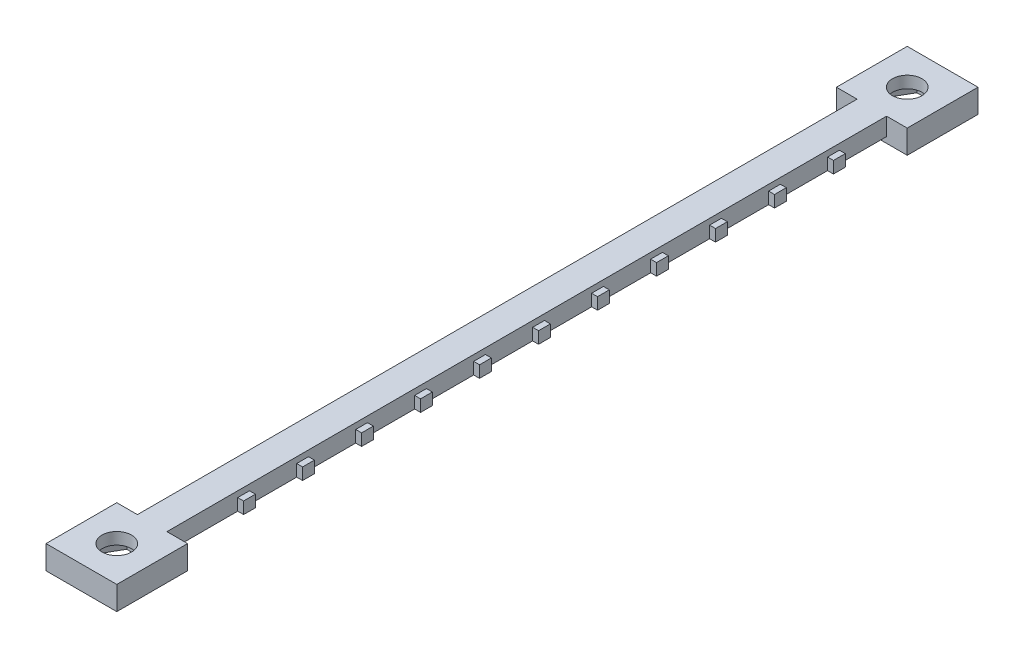
SolidWorks part; units mm, degrees
ref_plane "Front Plane" through (0, 0, 0) normal (0, 0, 1) x (1, 0, 0)
ref_plane "Top Plane" through (0, 0, 0) normal (0, 1, 0) x (1, 0, 0)
ref_plane "Right Plane" through (0, 0, 0) normal (1, 0, 0) x (0, 0, -1)
sketch "Sketch1" plane through (0, 0, 0) normal (0, 1, 0) x (1, 0, 0)
  line L0 (7.2267, 6.096) -> (7.2267, 18.096)
  line L1 (12.2267, 6.096) -> (12.2267, 18.096)
  line L2 (7.2267, 128.096) -> (3.7267, 128.096)
  line L3 (12.2267, 128.096) -> (15.7267, 128.096)
  line L4 (3.7267, 128.096) -> (3.7267, 140.096)
  line L5 (15.7267, 128.096) -> (15.7267, 140.096)
  line L6 (3.7267, 140.096) -> (15.7267, 140.096)
  line L7 (7.2267, 6.096) -> (3.7267, 6.096)
  line L8 (12.2267, 6.096) -> (15.7267, 6.096)
  line L9 (3.7267, 6.096) -> (3.7267, -5.904)
  line L10 (15.7267, 6.096) -> (15.7267, -5.904)
  line L11 (3.7267, -5.904) -> (15.7267, -5.904)
  line L12 (7.2267, 120.096) -> (7.2267, 128.096)
  line L13 (7.2267, 6.096) -> (7.2267, 128.096) construction
  line L14 (-994.5233, 128.096) -> (49005.4767, 128.096) construction
  line L15 (6.2267, 120.096) -> (7.2267, 120.096)
  line L18 (6.2267, 118.096) -> (7.2267, 118.096)
  line L19 (6.2267, 110.096) -> (7.2267, 110.096)
  line L20 (6.2267, 108.096) -> (7.2267, 108.096)
  line L21 (6.2267, 100.096) -> (7.2267, 100.096)
  line L22 (6.2267, 98.096) -> (7.2267, 98.096)
  line L23 (6.2267, 90.096) -> (7.2267, 90.096)
  line L24 (6.2267, 88.096) -> (7.2267, 88.096)
  line L25 (6.2267, 80.096) -> (7.2267, 80.096)
  line L26 (6.2267, 78.096) -> (7.2267, 78.096)
  line L27 (6.2267, 70.096) -> (7.2267, 70.096)
  line L28 (6.2267, 68.096) -> (7.2267, 68.096)
  line L29 (6.2267, 60.096) -> (7.2267, 60.096)
  line L30 (6.2267, 58.096) -> (7.2267, 58.096)
  line L31 (6.2267, 50.096) -> (7.2267, 50.096)
  line L32 (6.2267, 48.096) -> (7.2267, 48.096)
  line L33 (6.2267, 40.096) -> (7.2267, 40.096)
  line L34 (6.2267, 38.096) -> (7.2267, 38.096)
  line L35 (6.2267, 30.096) -> (7.2267, 30.096)
  line L36 (6.2267, 28.096) -> (7.2267, 28.096)
  line L37 (6.2267, 20.096) -> (7.2267, 20.096)
  line L38 (6.2267, 18.096) -> (7.2267, 18.096)
  line L39 (-994.5233, 118.096) -> (49005.4767, 118.096) construction
  line L40 (-994.5233, 120.096) -> (49005.4767, 120.096) construction
  line L41 (12.2267, 120.096) -> (12.2267, 128.096)
  line L42 (12.2267, 6.096) -> (12.2267, 128.096) construction
  line L43 (6.2267, 118.096) -> (6.2267, 120.096)
  line L44 (12.2267, 118.096) -> (13.2267, 118.096)
  line L45 (12.2267, 120.096) -> (13.2267, 120.096)
  line L46 (7.2267, 110.096) -> (7.2267, 118.096)
  line L47 (12.2267, 110.096) -> (12.2267, 118.096)
  line L48 (13.2267, 118.096) -> (13.2267, 120.096)
  line L49 (-994.5233, 110.096) -> (49005.4767, 110.096) construction
  line L50 (-994.5233, 108.096) -> (49005.4767, 108.096) construction
  line L51 (13.2267, 108.096) -> (13.2267, 110.096)
  line L52 (-994.5233, 100.096) -> (49005.4767, 100.096) construction
  line L53 (12.2267, 110.096) -> (13.2267, 110.096)
  line L54 (12.2267, 108.096) -> (13.2267, 108.096)
  line L55 (12.2267, 100.096) -> (13.2267, 100.096)
  line L56 (12.2267, 98.096) -> (13.2267, 98.096)
  line L57 (-994.5233, 98.096) -> (49005.4767, 98.096) construction
  line L58 (12.2267, 90.096) -> (13.2267, 90.096)
  line L59 (-994.5233, 90.096) -> (49005.4767, 90.096) construction
  line L60 (12.2267, 88.096) -> (13.2267, 88.096)
  line L61 (-994.5233, 88.096) -> (49005.4767, 88.096) construction
  line L62 (12.2267, 80.096) -> (13.2267, 80.096)
  line L63 (-994.5233, 80.096) -> (49005.4767, 80.096) construction
  line L64 (12.2267, 78.096) -> (13.2267, 78.096)
  line L65 (-994.5233, 78.096) -> (49005.4767, 78.096) construction
  line L66 (12.2267, 70.096) -> (13.2267, 70.096)
  line L67 (-994.5233, 70.096) -> (49005.4767, 70.096) construction
  line L68 (12.2267, 68.096) -> (13.2267, 68.096)
  line L69 (-994.5233, 68.096) -> (49005.4767, 68.096) construction
  line L70 (12.2267, 60.096) -> (13.2267, 60.096)
  line L71 (-994.5233, 60.096) -> (49005.4767, 60.096) construction
  line L72 (12.2267, 58.096) -> (13.2267, 58.096)
  line L73 (-994.5233, 58.096) -> (49005.4767, 58.096) construction
  line L74 (12.2267, 50.096) -> (13.2267, 50.096)
  line L75 (-994.5233, 50.096) -> (49005.4767, 50.096) construction
  line L76 (12.2267, 48.096) -> (13.2267, 48.096)
  line L77 (-994.5233, 48.096) -> (49005.4767, 48.096) construction
  line L78 (12.2267, 40.096) -> (13.2267, 40.096)
  line L79 (-994.5233, 40.096) -> (49005.4767, 40.096) construction
  line L80 (12.2267, 38.096) -> (13.2267, 38.096)
  line L81 (-994.5233, 38.096) -> (49005.4767, 38.096) construction
  line L82 (12.2267, 30.096) -> (13.2267, 30.096)
  line L83 (-994.5233, 30.096) -> (49005.4767, 30.096) construction
  line L84 (12.2267, 28.096) -> (13.2267, 28.096)
  line L85 (-994.5233, 28.096) -> (49005.4767, 28.096) construction
  line L86 (12.2267, 20.096) -> (13.2267, 20.096)
  line L87 (-994.5233, 20.096) -> (49005.4767, 20.096) construction
  line L88 (12.2267, 18.096) -> (13.2267, 18.096)
  line L89 (-994.5233, 18.096) -> (49005.4767, 18.096) construction
  line L90 (13.2267, 18.096) -> (13.2267, 20.096)
  line L91 (6.2267, 108.096) -> (6.2267, 110.096)
  line L92 (12.2267, 100.096) -> (12.2267, 108.096)
  line L93 (7.2267, 100.096) -> (7.2267, 108.096)
  line L94 (7.2267, 90.096) -> (7.2267, 98.096)
  line L95 (12.2267, 90.096) -> (12.2267, 98.096)
  line L96 (13.2267, 98.096) -> (13.2267, 100.096)
  line L97 (6.2267, 98.096) -> (6.2267, 100.096)
  line L98 (12.2267, 80.096) -> (12.2267, 88.096)
  line L99 (7.2267, 80.096) -> (7.2267, 88.096)
  line L100 (7.2267, 70.096) -> (7.2267, 78.096)
  line L101 (12.2267, 70.096) -> (12.2267, 78.096)
  line L102 (12.2267, 60.096) -> (12.2267, 68.096)
  line L103 (7.2267, 60.096) -> (7.2267, 68.096)
  line L104 (13.2267, 88.096) -> (13.2267, 90.096)
  line L105 (13.2267, 78.096) -> (13.2267, 80.096)
  line L106 (13.2267, 68.096) -> (13.2267, 70.096)
  line L107 (13.2267, 58.096) -> (13.2267, 60.096)
  line L108 (6.2267, 58.096) -> (6.2267, 60.096)
  line L109 (6.2267, 68.096) -> (6.2267, 70.096)
  line L110 (6.2267, 78.096) -> (6.2267, 80.096)
  line L111 (6.2267, 88.096) -> (6.2267, 90.096)
  line L112 (12.2267, 50.096) -> (12.2267, 58.096)
  line L113 (7.2267, 50.096) -> (7.2267, 58.096)
  line L114 (7.2267, 40.096) -> (7.2267, 48.096)
  line L115 (12.2267, 40.096) -> (12.2267, 48.096)
  line L116 (7.2267, 30.096) -> (7.2267, 38.096)
  line L117 (12.2267, 30.096) -> (12.2267, 38.096)
  line L118 (7.2267, 20.096) -> (7.2267, 28.096)
  line L119 (12.2267, 20.096) -> (12.2267, 28.096)
  line L120 (6.2267, 18.096) -> (6.2267, 20.096)
  line L121 (6.2267, 28.096) -> (6.2267, 30.096)
  line L122 (6.2267, 38.096) -> (6.2267, 40.096)
  line L123 (6.2267, 48.096) -> (6.2267, 50.096)
  line L124 (13.2267, 48.096) -> (13.2267, 50.096)
  line L125 (13.2267, 28.096) -> (13.2267, 30.096)
  line L126 (13.2267, 38.096) -> (13.2267, 40.096)
  point P20 (5.4767, 128.096)
  dimension "D1" = 5
  dimension "D4" = 8
  dimension "D5" = 2
  dimension "D6" = 10
  dimension "D7" = 20
  dimension "D8" = 40
  dimension "D9" = 40
extrude "Boss-Extrude1" add sketch "Sketch1" along normal blind 2
sketch "Sketch2" plane through (0, 2, 0) normal (0, 1, 0) x (1, 0, 0)
  line L0 (3.7267, 140.096) -> (15.7267, 140.096)
  line L1 (15.7267, 140.096) -> (15.7267, 128.096)
  line L2 (15.7267, 128.096) -> (12.2267, 128.096)
  line L3 (12.2267, 128.096) -> (15.7267, 128.096) construction
  line L4 (12.2267, 128.096) -> (12.2267, 6.096)
  line L5 (12.2267, 6.096) -> (15.7267, 6.096)
  line L6 (15.7267, 6.096) -> (15.7267, -5.904)
  line L7 (3.7267, -5.904) -> (15.7267, -5.904) construction
  line L8 (15.7267, -5.904) -> (15.7267, 6.096) construction
  line L9 (15.7267, -5.904) -> (3.7267, -5.904)
  line L10 (3.7267, 6.096) -> (3.7267, -5.904) construction
  line L11 (3.7267, -5.904) -> (3.7267, 6.096)
  line L12 (3.7267, 6.096) -> (7.2267, 6.096)
  line L13 (7.2267, 6.096) -> (7.2267, 128.096)
  line L14 (7.2267, 128.096) -> (3.7267, 128.096)
  line L15 (3.7267, 128.096) -> (7.2267, 128.096) construction
  line L16 (3.7267, 140.096) -> (3.7267, 128.096) construction
  line L17 (3.7267, 128.096) -> (3.7267, 140.096)
extrude "Boss-Extrude2" add sketch "Sketch2" along normal blind 1
sketch "Sketch3" plane through (0, 0, 0) normal (0, -1, 0) x (-1, 0, 0)
  line L0 (-15.7267, 128.096) -> (-3.7267, 128.096)
  line L1 (-12.2267, 128.096) -> (-15.7267, 128.096) construction
  line L2 (-15.7267, 128.096) -> (-15.7267, 140.096) construction
  line L3 (-3.7267, 128.096) -> (-3.7267, 140.096)
  line L4 (-3.7267, 140.096) -> (-3.7267, 128.096) construction
  line L5 (-15.7267, 140.096) -> (-3.7267, 140.096) construction
  line L6 (-3.7267, 140.096) -> (-15.7267, 140.096)
  line L7 (-15.7267, 140.096) -> (-15.7267, 128.096)
  line L8 (-3.7267, -5.904) -> (-3.7267, 6.096)
  line L9 (-3.7267, 6.096) -> (-15.7267, 6.096)
  line L10 (-15.7267, 6.096) -> (-15.7267, -5.904)
  line L11 (-15.7267, -5.904) -> (-3.7267, -5.904)
extrude "Boss-Extrude3" add sketch "Sketch3" along normal blind 1 contours L11 L8 L9 L10 | L7 L0 L3 L6
sketch "Sketch4" plane through (0, -1, 0) normal (0, -1, 0) x (-1, 0, 0)
  line L0 (-1015.7267, 134.096) -> (48984.2733, 134.096) construction
  line L1 (-15.7267, 140.096) -> (-15.7267, 128.096) construction
  line L2 (-9.7267, -859.904) -> (-9.7267, 49140.096) construction
  line L3 (-3.7267, 140.096) -> (-15.7267, 140.096) construction
  line L4 (-1015.7267, 0.096) -> (48984.2733, 0.096) construction
  line L11 (-7.3651, 138.096) -> (-11.9839, 138.096)
  line L12 (-11.9839, 138.096) -> (-14.2933, 134.096)
  line L13 (-14.2933, 134.096) -> (-11.9839, 130.096)
  line L14 (-11.9839, 130.096) -> (-7.3651, 130.096)
  line L15 (-7.3651, 130.096) -> (-5.0557, 134.096)
  line L16 (-5.0557, 134.096) -> (-7.3651, 138.096)
  line L17 (-15.7267, 6.096) -> (-15.7267, -5.904) construction
  line L19 (-7.4173, 4.096) -> (-12.0361, 4.096)
  line L20 (-12.0361, 4.096) -> (-14.3455, 0.096)
  line L21 (-14.3455, 0.096) -> (-12.0361, -3.904)
  line L22 (-12.0361, -3.904) -> (-7.4173, -3.904)
  line L23 (-7.4173, -3.904) -> (-5.1079, 0.096)
  line L24 (-5.1079, 0.096) -> (-7.4173, 4.096)
  circle A1 centre (-9.6745, 134.096) radius 4 construction
  circle A2 centre (-9.7267, 0.096) radius 4 construction
  point P5 (-15.7267, 134.096)
  point P10 (-9.7267, 140.096)
  point P31 (-15.7267, 0.096)
extrude "Cut-Extrude1" cut sketch "Sketch4" against normal blind 2 contours L11 L12 L13 L14 L15 L16 | L19 L20 L21 L22 L23 L24
sketch "Sketch5" plane through (0, 1, 0) normal (0, -1, 0) x (-1, 0, 0)
  line L0 (-1005.0557, 134.096) -> (48994.9443, 134.096) construction
  line L1 (-1005.1079, 0.096) -> (48994.8921, 0.096) construction
  line L2 (-9.7267, -995.904) -> (-9.7267, 49004.096) construction
  line L3 (-7.4173, 4.096) -> (-12.0361, 4.096) construction
  circle A0 centre (-9.7267, 0.096) radius 2.5
  circle A1 centre (-9.7267, 134.096) radius 2.5
  point P11 (-9.7267, 4.096)
extrude "Cut-Extrude2" cut sketch "Sketch5" against normal blind 5 contours A1 | A0
